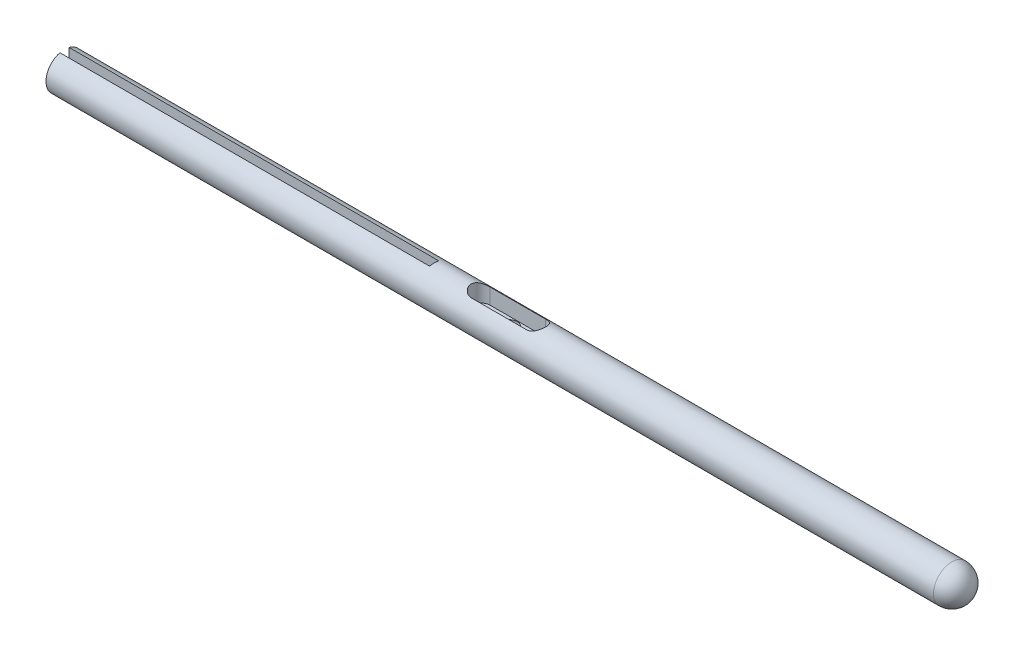
SolidWorks part; units mm, degrees
ref_plane "Front Plane" through (0, 0, 0) normal (0, 0, 1) x (1, 0, 0)
ref_plane "Top Plane" through (0, 0, 0) normal (0, 1, 0) x (1, 0, 0)
ref_plane "Right Plane" through (0, 0, 0) normal (1, 0, 0) x (0, 0, -1)
sketch "Sketch1" plane through (0, 0, 0) normal (1, 0, 0) x (0, 0, -1)
  circle A0 centre (0, 0) radius 3.175
  dimension "D1" = 6.35
extrude "Boss-Extrude1" add sketch "Sketch1" along normal blind 152.4
sketch "Sketch2" plane through (0, 0, 0) normal (0, 0, 1) x (1, 0, 0)
  line L1 (152.4, 3.175) -> (152.4, 0)
  line L2 (152.4, 0) -> (155.575, 0)
  arc A0 (152.4, 3.175) -> (155.575, 0) centre (152.4, 0) cw
  dimension "D1" = 3.175
ref_axis "Axis1" through (152.4, 0, 0) along (-1, 0, 0)
revolve "Revolve1" add sketch "Sketch2" angle 360 about axis through (152.4, 0, 0) along (-1, 0, 0)
sketch "Sketch3" plane through (0, 0, 0) normal (-1, 0, 0) x (0, 0, 1)
  line L1 (-0.7938, 3.175) -> (0.7937, 3.175)
  line L2 (-0.7938, 3.175) -> (-0.7937, -3.175)
  line L3 (-0.7937, -3.175) -> (0.7938, -3.175)
  line L4 (0.7937, 3.175) -> (0.7938, -3.175)
  dimension "D1" = 1.5875
  dimension "D2" = 0.7937
  dimension "D3" = 6.35
  dimension "D4" = 3.175
extrude "Cut-Extrude1" cut sketch "Sketch3" against normal blind 63.5
sketch "Sketch4" plane through (0, 0, 0) normal (0, 1, 0) x (1, 0, 0)
  line L1 (80.9625, 1.6718) -> (71.4375, 1.6718)
  line L2 (0, -0.7937) -> (0, -3.175) construction
  line L3 (80.9625, -1.5962) -> (71.4375, -1.5962)
  arc A0 (71.4375, 1.6718) -> (71.4375, -1.5962) centre (71.4375, 0.0378) ccw
  arc A1 (80.9625, 1.6718) -> (80.9625, -1.5962) centre (80.9625, 0.0378) cw
  dimension "D2" = 9.525
  dimension "D1" = 3.2679
  dimension "D3" = 71.4375
extrude "Cut-Extrude2" cut sketch "Sketch4" along normal blind 3.175
hole_wizard "#32 (0.116) Diameter Hole1" positions "Sketch6" profile "Sketch5" hole size "#32" standard "Ansi Inch"
sketch "Sketch6" plane through (0, 0, 0) normal (0, 1, 0) x (-1, 0, 0)
  line L0 (-80.9625, -1.6718) -> (-71.4375, -1.6718) construction
  arc A0 (-71.4375, -1.6718) -> (-71.4375, 1.5962) centre (-71.4375, -0.0378) ccw construction
  point P0 (-76.2, -0.0843)
  dimension "D1" = 1.5875
  dimension "D2" = 4.7625
sketch "Sketch5" plane through (76.2, 0, -0.0843) normal (1, 0, 0) x (0, 0, 1)
  line L0 (0, 0) -> (0, 26.2852)
  line L1 (0, 26.2852) -> (1.4732, 25.4)
  line L2 (1.4732, 25.4) -> (1.4732, 0)
  line L5 (1.4732, 0) -> (0, 0)
  line L10 (0, 26.2852) -> (-1.4732, 25.4) construction
  line L11 (0, -6.35) -> (0, 107.95) construction
  dimension "Hole Dia." = 2.9464
  dimension "Hole Depth" = 25.4
  dimension "Drill Angle" = 118
